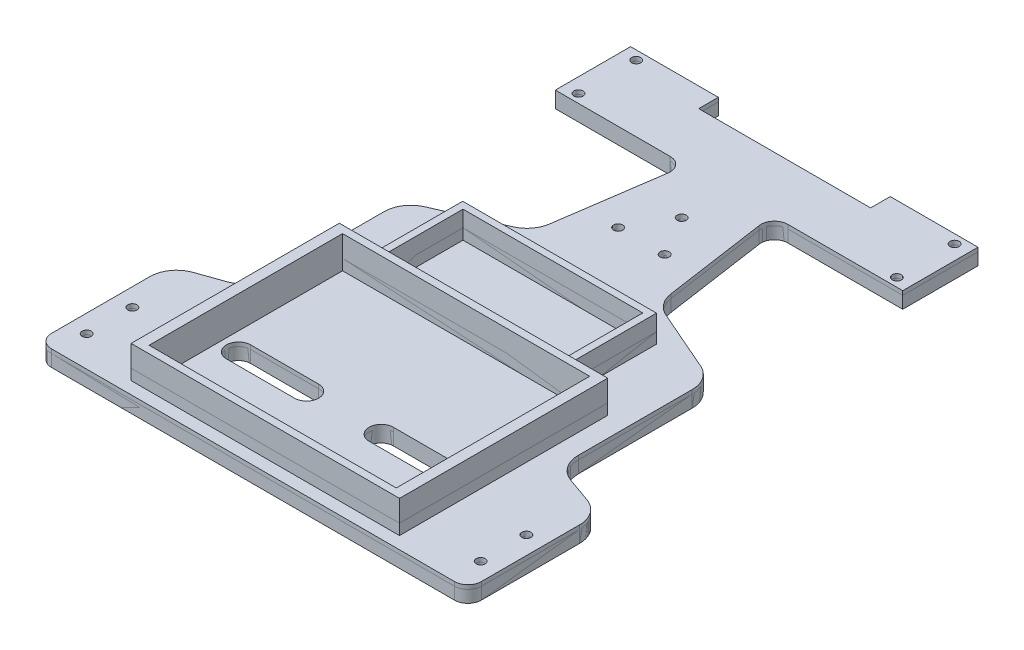
SolidWorks part; units mm, degrees
ref_plane "Front Plane" through (0, 0, 0) normal (0, 0, 1) x (1, 0, 0)
ref_plane "Top Plane" through (0, 0, 0) normal (0, 1, 0) x (1, 0, 0)
ref_plane "Right Plane" through (0, 0, 0) normal (1, 0, 0) x (0, 0, -1)
sketch "Sketch1" plane through (0, 0, 0) normal (0, 1, 0) x (1, 0, 0)
  line L1 (0, 123.1189) -> (0, -114.6431) construction
  line L5 (-80, -40.5061) -> (-80, -77.076)
  line L6 (-75, -82.076) -> (75, -82.076)
  line L28 (-51.3397, 33.1936) -> (-28.4659, 43.1635)
  line L36 (51.3397, 33.1936) -> (28.4487, 43.171)
  line L38 (-16.9584, 89.3848) -> (-22.566, 50.8891)
  line L39 (80, -40.5061) -> (80, -77.076)
  line L41 (-57.3441, 24.0265) -> (-57.3441, -18.3632)
  line L43 (57.3441, 24.0265) -> (57.3441, -18.3632)
  line L44 (-73.325, -31.075) -> (-64.0191, -27.7942)
  line L45 (64.0191, -27.7942) -> (73.325, -31.075)
  line L50 (-64.6552, 123.1189) -> (-64.6552, 95.1056)
  line L52 (64.6552, 123.1189) -> (64.6552, 95.1056)
  line L54 (16.9584, 89.3848) -> (22.553, 50.8682)
  line L55 (-64.6552, 95.1056) -> (-21.9062, 95.1056)
  line L56 (21.9062, 95.1056) -> (64.6552, 95.1056)
  line L61 (-32, 115.8044) -> (32, 115.8044)
  line L62 (32, 115.8044) -> (32, 123.1189)
  line L63 (-32, 115.8044) -> (-32, 123.1189)
  line L64 (-32, 123.1189) -> (-64.6552, 123.1189)
  line L65 (32, 123.1189) -> (64.6552, 123.1189)
  line L69 (13.8917, -48.2392) -> (39.2357, -48.2392) construction
  line L70 (13.8917, -43.7228) -> (39.2357, -43.7228)
  line L71 (13.8917, -52.7555) -> (39.2357, -52.7555)
  line L75 (-13.8917, -48.2392) -> (-39.2357, -48.2392) construction
  line L76 (-13.8917, -43.7228) -> (-39.2357, -43.7228)
  line L77 (-13.8917, -52.7555) -> (-39.2357, -52.7555)
  arc A1 (80, -77.076) -> (75, -82.076) centre (75, -77.076) cw
  arc A2 (-80, -77.076) -> (-75, -82.076) centre (-75, -77.076) ccw
  arc A5 (-28.4659, 43.1635) -> (-22.566, 50.8891) centre (-32.4616, 52.3305) ccw
  arc A6 (22.553, 50.8682) -> (28.4487, 43.171) centre (32.4444, 52.338) ccw
  arc A14 (-80, -40.5061) -> (-73.325, -31.075) centre (-70, -40.5061) cw
  arc A15 (73.325, -31.075) -> (80, -40.5061) centre (70, -40.5061) cw
  arc A16 (57.3441, -18.3632) -> (64.0191, -27.7942) centre (67.3441, -18.3632) ccw
  arc A17 (51.3397, 33.1936) -> (57.3441, 24.0265) centre (47.3441, 24.0265) cw
  arc A18 (-51.3397, 33.1936) -> (-57.3441, 24.0265) centre (-47.3441, 24.0265) ccw
  arc A19 (-57.3441, -18.3632) -> (-64.0191, -27.7942) centre (-67.3441, -18.3632) cw
  circle A20 centre (-59.25, 119.8044) radius 1.7
  circle A21 centre (-59.25, 98.3044) radius 1.7
  circle A22 centre (59.25, 98.3044) radius 1.7
  circle A23 centre (59.25, 119.8044) radius 1.7
  arc A24 (-16.9584, 89.3848) -> (-21.9062, 95.1056) centre (-21.9062, 90.1056) ccw
  arc A25 (16.9584, 89.3848) -> (21.9062, 95.1056) centre (21.9062, 90.1056) cw
  circle A26 centre (-73.325, -53.6654) radius 1.7
  circle A27 centre (-73.325, -70.6654) radius 1.7
  circle A28 centre (73.325, -70.6654) radius 1.7
  circle A29 centre (73.325, -53.6654) radius 1.7
  arc A32 (13.8917, -43.7228) -> (13.8917, -52.7555) centre (13.8917, -48.2392) ccw
  arc A33 (39.2357, -52.7555) -> (39.2357, -43.7228) centre (39.2357, -48.2392) ccw
  arc A36 (-13.8917, -43.7228) -> (-13.8917, -52.7555) centre (-13.8917, -48.2392) cw
  arc A37 (-39.2357, -52.7555) -> (-39.2357, -43.7228) centre (-39.2357, -48.2392) cw
  circle A39 centre (0, 77.4812) radius 1.7
  circle A40 centre (-8.6603, 62.4812) radius 1.7
  circle A41 centre (8.6603, 62.4812) radius 1.7
  point P7 (0, 98.3044)
  point P14 (0, -82.076)
  point P17 (0, -82.076)
  point P24 (-23.3677, 45.3856)
  point P29 (80, -45.2283)
  point P32 (80, -82.076)
  point P35 (-80, -82.076)
  point P38 (-80, -45.2283)
  point P39 (23.3677, 45.3856)
  point P42 (50, 34.4201)
  point P44 (-80, -33.4284)
  point P47 (80, -33.4284)
  point P51 (-50, 34.4201)
  point P52 (57.3441, -25.4409)
  point P55 (57.3441, 30.5765)
  point P58 (-57.3441, 30.5765)
  point P61 (-57.3441, -25.4409)
  point P66 (0, 95.1492)
  point P67 (0, 119.8044)
  point P69 (0, 125.9925)
  point P73 (0, 115.8044)
  point P76 (-16.1251, 95.1056)
  point P79 (16.1251, 95.1056)
  point P95 (26.5637, -48.2392)
  point P101 (0, 67.4812)
  point P109 (-26.5637, -48.2392)
  dimension "D7" = 10
  dimension "D8" = 64
  dimension "D4" = 5
  dimension "D1" = 160
  dimension "D2" = 59.25
  dimension "D3" = 0
  dimension "D5" = 36.8477
  dimension "D6" = 116.4961
extrude "Boss-Extrude2" add sketch "Sketch1" along normal blind 6
sketch "Sketch2" plane through (0, 6, 0) normal (0, 1, 0) x (1, 0, 0)
  line L1 (46, -2.7522) -> (-46, -2.7522)
  line L2 (46, -2.7522) -> (46, -74.7522)
  line L3 (46, -74.7522) -> (-46, -74.7522)
  line L4 (-46, -2.7522) -> (-46, -74.7522)
  line L5 (46, -2.7522) -> (-46, -74.7522) construction
  line L6 (46, -74.7522) -> (-46, -2.7522) construction
  line L7 (-49.9483, -77.5045) -> (49.9483, -77.5045)
  line L8 (-49.9483, -77.5045) -> (-49.9483, 0)
  line L9 (-49.9483, 0) -> (49.9483, 0)
  line L10 (49.9483, -77.5045) -> (49.9483, 0)
  line L11 (-49.9483, -77.5045) -> (49.9483, 0) construction
  line L12 (-49.9483, 0) -> (49.9483, -77.5045) construction
  point P0 (0, -38.7522)
  point P5 (0, -38.7522)
  dimension "D1" = 92
  dimension "D2" = 72
  dimension "D3" = 3.9483
sketch "Sketch4" plane through (0, 6, 0) normal (0, 1, 0) x (1, 0, 0)
extrude "Boss-Extrude3" add sketch "Sketch2" along normal blind 12
sketch "Sketch8" plane through (0, 6, 0) normal (0, 1, 0) x (1, 0, 0)
  line L1 (-36.0682, 0.0375) -> (36.0682, 0.0375)
  line L2 (-36.0682, 0.0375) -> (-36.0682, 32.0375)
  line L3 (-36.0682, 32.0375) -> (36.0682, 32.0375)
  line L4 (36.0682, 0.0375) -> (36.0682, 32.0375)
  line L5 (-36.0682, 0.0375) -> (36.0682, 32.0375) construction
  line L6 (-36.0682, 32.0375) -> (36.0682, 0.0375) construction
  line L9 (33.4608, 29.5424) -> (-33.4608, 29.5424)
  line L10 (33.4608, 29.5424) -> (33.4608, 0.0375)
  line L11 (33.4608, 0.0375) -> (-33.4608, 0.0375)
  line L12 (-33.4608, 29.5424) -> (-33.4608, 0.0375)
  point P0 (0, 16.0375)
  point P10 (0, 29.5424)
  dimension "D1" = 72.1363
  dimension "D2" = 32
  dimension "D3" = 66.9216
extrude "Boss-Extrude7" add sketch "Sketch8" along normal blind 10 contours L12 L9 L10 L1 L4 L3 L2 region at (-35.279, 6, -16.0375)
extrude "Boss-Extrude9" add sketch "Sketch2<3>" along normal blind 4 and the other way blind 2 separate body
sketch "Sketch2<3>" plane through (0, 6, 0) normal (0, 1, 0) x (1, 0, 0) same geometry as "Sketch2"
extrude "Boss-Extrude10" add sketch "Sketch1<3>" along normal blind 0.001 and the other way blind 0.01
sketch "Sketch1<3>" plane through (0, 0, 0) normal (0, 1, 0) x (1, 0, 0) same geometry as "Sketch1"
extrude "Boss-Extrude11" add sketch "Sketch8<9>" along normal blind 4 and the other way blind 2 contours L12 L9 L10 L1 L4 L3 L2 region at (-35.279, 6, -16.0375)
sketch "Sketch8<9>" plane through (0, 6, 0) normal (0, 1, 0) x (1, 0, 0) same geometry as "Sketch8"
extrude "Boss-Extrude13" add sketch "Sketch1<5>" along normal blind 4.5
sketch "Sketch1<5>" plane through (0, 0, 0) normal (0, 1, 0) x (1, 0, 0) same geometry as "Sketch1"
